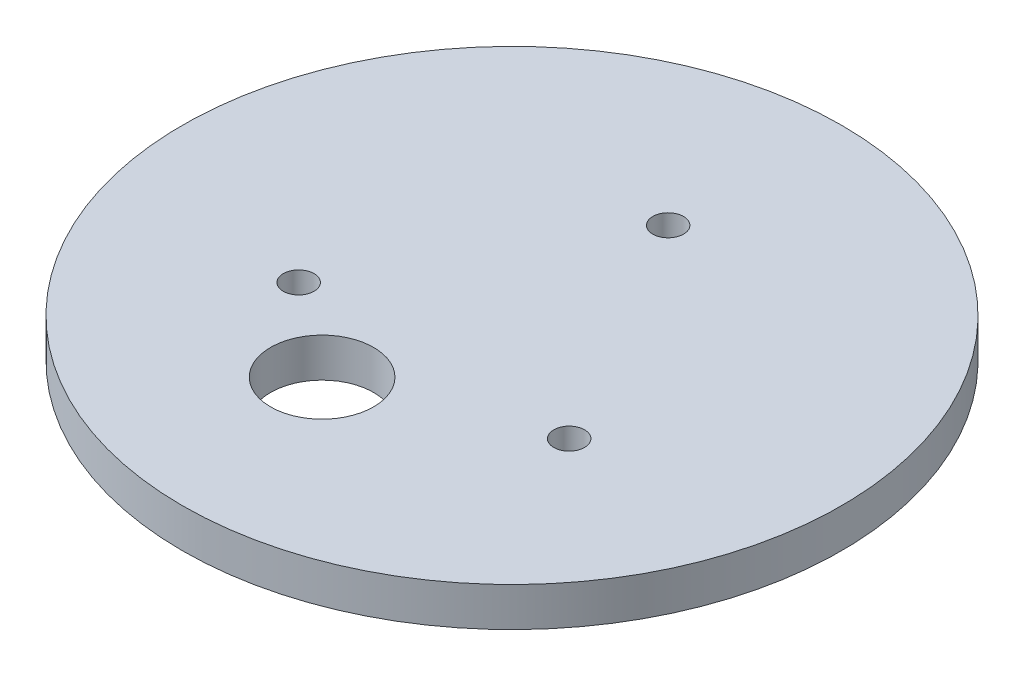
SolidWorks part; units mm, degrees
ref_plane "Front Plane" through (0, 0, 0) normal (0, 0, 1) x (1, 0, 0)
ref_plane "Top Plane" through (0, 0, 0) normal (0, 1, 0) x (1, 0, 0)
ref_plane "Right Plane" through (0, 0, 0) normal (1, 0, 0) x (0, 0, -1)
sketch "Sketch2" plane through (0, 0, 0) normal (0, 1, 0) x (1, 0, 0)
  circle A0 centre (0, 0) radius 26.8
  dimension "D1" = 53.6
extrude "Boss-Extrude1" add sketch "Sketch2" along normal blind 3.175
sketch "Sketch3" plane through (0, 3.175, 0) normal (0, 1, 0) x (1, 0, 0)
  line L0 (0, 0) -> (0, 26.8) construction
  line L1 (0, 0) -> (23.2095, -13.4) construction
  line L2 (0, 0) -> (-23.2095, -13.4) construction
  circle A0 centre (0, 0) radius 26.8 construction
  circle A7 centre (0, 12.7) radius 1.25
  circle A8 centre (-10.9985, -6.35) radius 1.25
  circle A9 centre (10.9985, -6.35) radius 1.25
  dimension "D16" = 12.7
  dimension "D19" = 12.7
  dimension "D1" = 120
  dimension "D2" = 120
  dimension "D18" = 12.7
extrude "Cut-Extrude1" cut sketch "Sketch3" against normal blind 3.175 contours A8 | A7 | A9 region at (0, 3.175, -12.7) region at (-10.9985, 3.175, 6.35) region at (10.9985, 3.175, 6.35)
sketch "Sketch4" plane through (0, 3.175, 0) normal (0, 1, 0) x (1, 0, 0)
  circle A0 centre (-3.3785, -12.065) radius 4.191
  circle A1 centre (10.9985, -6.35) radius 1.25 construction
  circle A3 centre (-10.9985, -6.35) radius 1.25 construction
  dimension "D1" = 8.382
  dimension "D2" = 7.62
  dimension "D3" = 5.715
extrude "Cut-Extrude2" cut sketch "Sketch4" against normal blind 7.62
